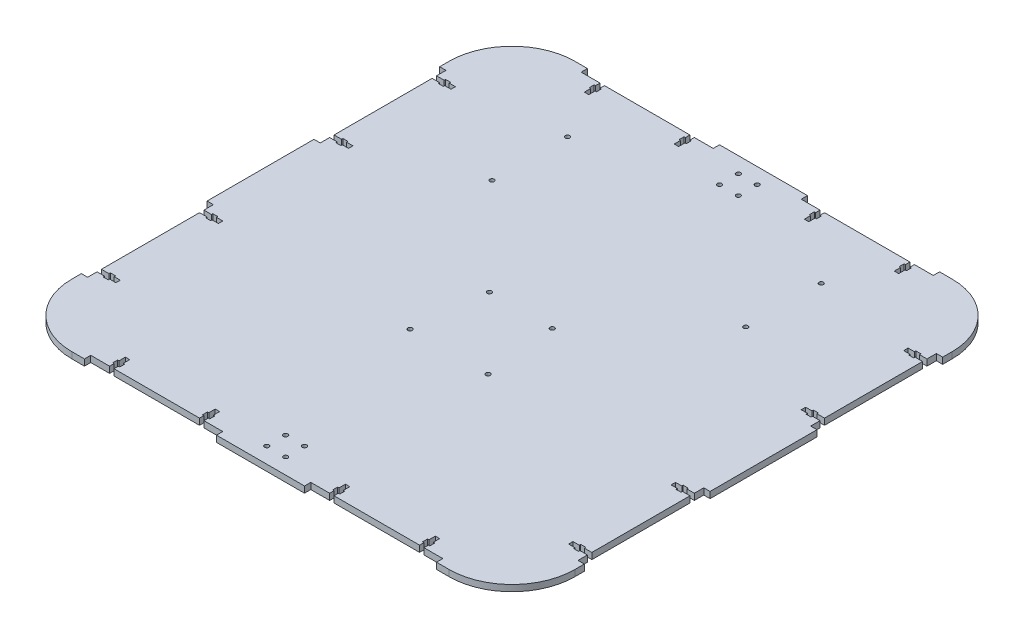
SolidWorks part; units mm, degrees
ref_plane "Front Plane" through (0, 0, 0) normal (0, 0, 1) x (1, 0, 0)
ref_plane "Top Plane" through (0, 0, 0) normal (0, 1, 0) x (1, 0, 0)
ref_plane "Right Plane" through (0, 0, 0) normal (1, 0, 0) x (0, 0, -1)
sketch "Sketch1" plane through (0, 0, 0) normal (0, 1, 0) x (1, 0, 0)
  line L0 (0, -1000) -> (0, 49000) construction
  line L9 (-1000, 0) -> (49000, 0) construction
  line L10 (-10, 190) -> (10, 190)
  line L11 (-10, 190) -> (-10, 170)
  line L12 (-10, 170) -> (10, 170)
  line L13 (10, 190) -> (10, 170)
  line L14 (-1010, 180) -> (48990, 180) construction
  line L15 (-1010, -180) -> (48990, -180) construction
  line L16 (0, 1000) -> (0, -49000) construction
  line L17 (-10, -170) -> (10, -170)
  line L18 (10, -190) -> (10, -170)
  line L19 (-10, -190) -> (10, -190)
  line L20 (-10, -190) -> (-10, -170)
  line L22 (-200, 200) -> (200, 200)
  line L23 (-200, 200) -> (-200, -200)
  line L24 (-200, -200) -> (200, -200)
  line L25 (200, 200) -> (200, -200)
  circle A0 centre (0, 0) radius 200 construction
  circle A1 centre (-7.5, 187.5) radius 1.75
  circle A2 centre (7.5, 187.5) radius 1.75
  circle A3 centre (7.5, 172.5) radius 1.75
  circle A4 centre (-7.5, 172.5) radius 1.75
  circle A5 centre (7.5, -187.5) radius 1.75
  circle A6 centre (-7.5, -187.5) radius 1.75
  circle A7 centre (-7.5, -172.5) radius 1.75
  circle A8 centre (7.5, -172.5) radius 1.75
  point P19 (0, 190)
  point P22 (-10, 180)
  dimension "D1" = 400
  dimension "D7" = 3.5
  dimension "D5" = 20
  dimension "D6" = 180
  dimension "D8" = 2.5
  dimension "D9" = 2.5
extrude "Boss-Extrude2" add sketch "Sketch1" along normal blind 5 contours L25 L22 L23 L24 L10 L13 L12 L11 L19 L20 L17 L18 | L20 L19 L18 L17 A6 A5 A7 A8 | L13 L10 L11 L12 A2 A1 A3 A4 region at (0, 0, -180) region at (0, 0, 180) region at (0, 0, 0)
fillet "Fillet1" radius 50 4 edges at (200, 2.5, -200) (200, 2.5, 200) (-200, 2.5, 200) (-200, 2.5, -200)
sketch "Sketch10" plane through (0, 5, 0) normal (0, 1, 0) x (1, 0, 0)
  line L0 (-150, -200) -> (150, -200) construction
  line L1 (-125, -200) -> (-121.5, -200)
  line L2 (-125, -200) -> (-125, -191.5)
  line L3 (-125, -182.5) -> (-121.5, -182.5)
  line L4 (-121.5, -200) -> (-121.5, -191.5)
  line L6 (-121.5, -187.5) -> (-120.4, -187.5)
  line L7 (-126.1, -187.5) -> (-125, -187.5)
  line L8 (-126.1, -187.5) -> (-126.1, -191.5)
  line L9 (-126.1, -191.5) -> (-125, -191.5)
  line L10 (-120.4, -187.5) -> (-120.4, -191.5)
  line L11 (-121.5, -191.5) -> (-120.4, -191.5)
  line L12 (-125, -187.5) -> (-125, -182.5)
  line L13 (-121.5, -187.5) -> (-121.5, -182.5)
  line L14 (-125, -187.5) -> (-121.5, -187.5) construction
  line L15 (-121.5, -191.5) -> (-125, -191.5) construction
  line L16 (-53.5, -200) -> (-50, -200)
  line L17 (-50, -200) -> (-50, -191.5)
  line L18 (-50, -191.5) -> (-48.9, -191.5)
  line L19 (-48.9, -187.5) -> (-48.9, -191.5)
  line L20 (-50, -187.5) -> (-48.9, -187.5)
  line L21 (-50, -187.5) -> (-50, -182.5)
  line L22 (-53.5, -182.5) -> (-50, -182.5)
  line L23 (-53.5, -187.5) -> (-53.5, -182.5)
  line L24 (-54.6, -187.5) -> (-53.5, -187.5)
  line L25 (-54.6, -187.5) -> (-54.6, -191.5)
  line L26 (-54.6, -191.5) -> (-53.5, -191.5)
  line L27 (-53.5, -200) -> (-53.5, -191.5)
  line L28 (-50, -191.5) -> (-53.5, -191.5) construction
  line L29 (-53.5, -187.5) -> (-50, -187.5) construction
  line L30 (0, -1200) -> (0, 48800) construction
  line L31 (-200, 150) -> (-200, -150) construction
  line L32 (121.5, -191.5) -> (125, -191.5) construction
  line L33 (125, -187.5) -> (121.5, -187.5) construction
  line L34 (125, -200) -> (125, -191.5)
  line L35 (126.1, -191.5) -> (125, -191.5)
  line L36 (126.1, -187.5) -> (126.1, -191.5)
  line L37 (126.1, -187.5) -> (125, -187.5)
  line L38 (125, -187.5) -> (125, -182.5)
  line L39 (125, -182.5) -> (121.5, -182.5)
  line L40 (121.5, -187.5) -> (121.5, -182.5)
  line L41 (121.5, -187.5) -> (120.4, -187.5)
  line L42 (120.4, -187.5) -> (120.4, -191.5)
  line L43 (121.5, -191.5) -> (120.4, -191.5)
  line L44 (121.5, -200) -> (121.5, -191.5)
  line L45 (125, -200) -> (121.5, -200)
  line L46 (53.5, -187.5) -> (50, -187.5) construction
  line L47 (50, -191.5) -> (53.5, -191.5) construction
  line L48 (53.5, -200) -> (53.5, -191.5)
  line L49 (54.6, -191.5) -> (53.5, -191.5)
  line L50 (54.6, -187.5) -> (54.6, -191.5)
  line L51 (54.6, -187.5) -> (53.5, -187.5)
  line L52 (53.5, -187.5) -> (53.5, -182.5)
  line L53 (53.5, -182.5) -> (50, -182.5)
  line L54 (50, -187.5) -> (50, -182.5)
  line L55 (50, -187.5) -> (48.9, -187.5)
  line L56 (48.9, -187.5) -> (48.9, -191.5)
  line L57 (50, -191.5) -> (48.9, -191.5)
  line L58 (50, -200) -> (50, -191.5)
  line L59 (53.5, -200) -> (50, -200)
  line L60 (-1000, 0) -> (49000, 0) construction
  line L61 (125, 200) -> (121.5, 200)
  line L62 (121.5, 200) -> (121.5, 191.5)
  line L63 (121.5, 191.5) -> (120.4, 191.5)
  line L64 (120.4, 187.5) -> (120.4, 191.5)
  line L65 (121.5, 187.5) -> (120.4, 187.5)
  line L66 (121.5, 187.5) -> (121.5, 182.5)
  line L67 (125, 182.5) -> (121.5, 182.5)
  line L68 (125, 187.5) -> (125, 182.5)
  line L69 (126.1, 187.5) -> (125, 187.5)
  line L70 (126.1, 187.5) -> (126.1, 191.5)
  line L71 (126.1, 191.5) -> (125, 191.5)
  line L72 (125, 200) -> (125, 191.5)
  line L73 (53.5, 200) -> (50, 200)
  line L74 (50, 200) -> (50, 191.5)
  line L75 (50, 191.5) -> (48.9, 191.5)
  line L76 (48.9, 187.5) -> (48.9, 191.5)
  line L77 (50, 187.5) -> (48.9, 187.5)
  line L78 (50, 187.5) -> (50, 182.5)
  line L79 (53.5, 182.5) -> (50, 182.5)
  line L80 (53.5, 187.5) -> (53.5, 182.5)
  line L81 (54.6, 187.5) -> (53.5, 187.5)
  line L82 (54.6, 187.5) -> (54.6, 191.5)
  line L83 (54.6, 191.5) -> (53.5, 191.5)
  line L84 (53.5, 200) -> (53.5, 191.5)
  line L85 (-53.5, 200) -> (-53.5, 191.5)
  line L86 (-54.6, 191.5) -> (-53.5, 191.5)
  line L87 (-54.6, 187.5) -> (-54.6, 191.5)
  line L88 (-54.6, 187.5) -> (-53.5, 187.5)
  line L89 (-53.5, 187.5) -> (-53.5, 182.5)
  line L90 (-53.5, 182.5) -> (-50, 182.5)
  line L91 (-50, 187.5) -> (-50, 182.5)
  line L92 (-50, 187.5) -> (-48.9, 187.5)
  line L93 (-48.9, 187.5) -> (-48.9, 191.5)
  line L94 (-50, 191.5) -> (-48.9, 191.5)
  line L95 (-50, 200) -> (-50, 191.5)
  line L96 (-53.5, 200) -> (-50, 200)
  line L97 (-125, 200) -> (-125, 191.5)
  line L98 (-126.1, 191.5) -> (-125, 191.5)
  line L99 (-126.1, 187.5) -> (-126.1, 191.5)
  line L100 (-126.1, 187.5) -> (-125, 187.5)
  line L101 (-125, 187.5) -> (-125, 182.5)
  line L102 (-125, 182.5) -> (-121.5, 182.5)
  line L103 (-121.5, 187.5) -> (-121.5, 182.5)
  line L104 (-121.5, 187.5) -> (-120.4, 187.5)
  line L105 (-120.4, 187.5) -> (-120.4, 191.5)
  line L106 (-121.5, 191.5) -> (-120.4, 191.5)
  line L107 (-121.5, 200) -> (-121.5, 191.5)
  line L108 (-125, 200) -> (-121.5, 200)
  point P11 (-123.25, -200)
  point P15 (-123.25, -191.5)
  point P16 (-123.25, -187.5)
  point P17 (-123.25, -182.5)
  point P33 (0, -200)
  dimension "D1" = 3.5
  dimension "D2" = 5.7
  dimension "D3" = 5
  dimension "D4" = 4
  dimension "D5" = 1.1
  dimension "D7" = 75
  dimension "D8" = 50
  dimension "D9" = 17.5
  dimension "D6" = 2
extrude "Cut-Extrude8" cut sketch "Sketch10" against normal blind 10
sketch "Sketch11" plane through (0, 5, 0) normal (0, 1, 0) x (1, 0, 0)
  line L0 (-150, -200) -> (-125, -200) construction
  line L1 (-140, -200) -> (-35, -200)
  line L2 (-140, -200) -> (-140, -195)
  line L3 (-140, -195) -> (-35, -195)
  line L4 (-35, -200) -> (-35, -195)
  line L5 (-50, -200) -> (-50, -191.5) construction
  line L6 (-125, -191.5) -> (-125, -200) construction
  line L7 (0, -1200) -> (0, 48800) construction
  line L8 (-50, -200) -> (50, -200) construction
  line L9 (-1200, 0) -> (48800, 0) construction
  line L10 (-200, 150) -> (-200, -150) construction
  line L11 (140, -195) -> (35, -195)
  line L12 (35, -200) -> (35, -195)
  line L13 (140, -200) -> (35, -200)
  line L14 (140, -200) -> (140, -195)
  line L15 (140, 200) -> (140, 195)
  line L16 (140, 200) -> (35, 200)
  line L17 (35, 200) -> (35, 195)
  line L18 (140, 195) -> (35, 195)
  line L19 (-140, 195) -> (-35, 195)
  line L20 (-35, 200) -> (-35, 195)
  line L21 (-140, 200) -> (-35, 200)
  line L22 (-140, 200) -> (-140, 195)
  point P15 (0, -200)
  point P20 (-200, 0)
  dimension "D1" = 5
  dimension "D2" = 15
  dimension "D3" = 15
extrude "Cut-Extrude9" cut sketch "Sketch11" against normal blind 10
sketch "Sketch12" plane through (0, 5, 0) normal (0, 1, 0) x (1, 0, 0)
  line L0 (-200, 150) -> (-200, -150) construction
  line L1 (-200, 135) -> (-189, 135)
  line L2 (-200, 135) -> (-200, 131.5)
  line L3 (-200, 131.5) -> (-189, 131.5)
  line L4 (-180, 135) -> (-180, 131.5)
  line L5 (-200, 53.5) -> (-189, 53.5)
  line L6 (-189, 131.5) -> (-189, 130.4)
  line L7 (-189, 136.1) -> (-185, 136.1)
  line L8 (-189, 136.1) -> (-189, 135)
  line L9 (-189, 130.4) -> (-185, 130.4)
  line L10 (-185, 136.1) -> (-185, 135)
  line L11 (-185, 131.5) -> (-185, 130.4)
  line L12 (-185, 135) -> (-180, 135)
  line L13 (-185, 131.5) -> (-180, 131.5)
  line L14 (-189, 135) -> (-189, 131.5) construction
  line L15 (-185, 131.5) -> (-185, 135) construction
  line L16 (-189, 54.6) -> (-189, 53.5)
  line L17 (-189, 54.6) -> (-185, 54.6)
  line L18 (-185, 54.6) -> (-185, 53.5)
  line L19 (-185, 53.5) -> (-180, 53.5)
  line L20 (-180, 53.5) -> (-180, 50)
  line L21 (-185, 50) -> (-180, 50)
  line L22 (-185, 50) -> (-185, 48.9)
  line L23 (-189, 48.9) -> (-185, 48.9)
  line L24 (-189, 50) -> (-189, 48.9)
  line L25 (-200, 50) -> (-189, 50)
  line L26 (-200, 53.5) -> (-200, 50)
  line L27 (-1200, 0) -> (48800, 0) construction
  line L28 (-200, -53.5) -> (-200, -50)
  line L29 (-200, -50) -> (-189, -50)
  line L30 (-189, -50) -> (-189, -48.9)
  line L31 (-189, -48.9) -> (-185, -48.9)
  line L32 (-185, -50) -> (-185, -48.9)
  line L33 (-185, -50) -> (-180, -50)
  line L34 (-180, -53.5) -> (-180, -50)
  line L35 (-185, -53.5) -> (-180, -53.5)
  line L36 (-185, -54.6) -> (-185, -53.5)
  line L37 (-189, -54.6) -> (-185, -54.6)
  line L38 (-189, -54.6) -> (-189, -53.5)
  line L39 (-200, -53.5) -> (-189, -53.5)
  line L40 (-200, -135) -> (-200, -131.5)
  line L41 (-200, -131.5) -> (-189, -131.5)
  line L42 (-189, -131.5) -> (-189, -130.4)
  line L43 (-189, -130.4) -> (-185, -130.4)
  line L44 (-185, -131.5) -> (-185, -130.4)
  line L45 (-185, -131.5) -> (-180, -131.5)
  line L46 (-180, -135) -> (-180, -131.5)
  line L47 (-185, -135) -> (-180, -135)
  line L48 (-185, -136.1) -> (-185, -135)
  line L49 (-189, -136.1) -> (-185, -136.1)
  line L50 (-189, -136.1) -> (-189, -135)
  line L51 (-200, -135) -> (-189, -135)
  line L52 (0, -1200) -> (0, 48800) construction
  line L53 (-35, -200) -> (35, -200) construction
  line L54 (200, -135) -> (189, -135)
  line L55 (189, -136.1) -> (189, -135)
  line L56 (189, -136.1) -> (185, -136.1)
  line L57 (185, -136.1) -> (185, -135)
  line L58 (185, -135) -> (180, -135)
  line L59 (180, -135) -> (180, -131.5)
  line L60 (185, -131.5) -> (180, -131.5)
  line L61 (185, -131.5) -> (185, -130.4)
  line L62 (189, -130.4) -> (185, -130.4)
  line L63 (189, -131.5) -> (189, -130.4)
  line L64 (200, -131.5) -> (189, -131.5)
  line L65 (200, -135) -> (200, -131.5)
  line L66 (200, -53.5) -> (189, -53.5)
  line L67 (189, -54.6) -> (189, -53.5)
  line L68 (189, -54.6) -> (185, -54.6)
  line L69 (185, -54.6) -> (185, -53.5)
  line L70 (185, -53.5) -> (180, -53.5)
  line L71 (180, -53.5) -> (180, -50)
  line L72 (185, -50) -> (180, -50)
  line L73 (185, -50) -> (185, -48.9)
  line L74 (189, -48.9) -> (185, -48.9)
  line L75 (189, -50) -> (189, -48.9)
  line L76 (200, -50) -> (189, -50)
  line L77 (200, -53.5) -> (200, -50)
  line L78 (200, 53.5) -> (200, 50)
  line L79 (200, 50) -> (189, 50)
  line L80 (189, 50) -> (189, 48.9)
  line L81 (189, 48.9) -> (185, 48.9)
  line L82 (185, 50) -> (185, 48.9)
  line L83 (185, 50) -> (180, 50)
  line L84 (180, 53.5) -> (180, 50)
  line L85 (185, 53.5) -> (180, 53.5)
  line L86 (185, 54.6) -> (185, 53.5)
  line L87 (189, 54.6) -> (185, 54.6)
  line L88 (189, 54.6) -> (189, 53.5)
  line L89 (200, 53.5) -> (189, 53.5)
  line L90 (200, 135) -> (200, 131.5)
  line L91 (200, 131.5) -> (189, 131.5)
  line L92 (189, 131.5) -> (189, 130.4)
  line L93 (189, 130.4) -> (185, 130.4)
  line L94 (185, 131.5) -> (185, 130.4)
  line L95 (185, 131.5) -> (180, 131.5)
  line L96 (180, 135) -> (180, 131.5)
  line L97 (185, 135) -> (180, 135)
  line L98 (185, 136.1) -> (185, 135)
  line L99 (189, 136.1) -> (185, 136.1)
  line L100 (189, 136.1) -> (189, 135)
  line L101 (200, 135) -> (189, 135)
  point P31 (-200, 0)
  point P60 (0, -200)
  dimension "D1" = 20
  dimension "D2" = 3.5
  dimension "D3" = 5.7
  dimension "D4" = 5
  dimension "D5" = 4
  dimension "D6" = 15
  dimension "D7" = 1.1
  dimension "D9" = 50
  dimension "D8" = 2
extrude "Cut-Extrude10" cut sketch "Sketch12" against normal blind 5
sketch "Sketch13" plane through (0, 5, 0) normal (0, 1, 0) x (1, 0, 0)
  line L0 (-200, 150) -> (-200, 135) construction
  line L1 (-200, 142.5) -> (-195, 142.5)
  line L2 (-200, 142.5) -> (-200, 42.5)
  line L3 (-200, 42.5) -> (-195, 42.5)
  line L4 (-195, 142.5) -> (-195, 42.5)
  line L6 (-200, 50) -> (-189, 50) construction
  line L7 (-1200, 0) -> (48800, 0) construction
  line L8 (-200, 50) -> (-200, -50) construction
  line L9 (0, -800) -> (0, 49200) construction
  line L10 (-35, 200) -> (35, 200) construction
  line L11 (-200, -42.5) -> (-195, -42.5)
  line L12 (-195, -142.5) -> (-195, -42.5)
  line L13 (-200, -142.5) -> (-195, -142.5)
  line L14 (-200, -142.5) -> (-200, -42.5)
  line L15 (0, 800) -> (0, -49200) construction
  line L16 (200, -142.5) -> (200, -42.5)
  line L17 (200, -142.5) -> (195, -142.5)
  line L18 (195, -142.5) -> (195, -42.5)
  line L19 (200, -42.5) -> (195, -42.5)
  line L20 (200, 42.5) -> (195, 42.5)
  line L21 (195, 142.5) -> (195, 42.5)
  line L22 (200, 142.5) -> (195, 142.5)
  line L23 (200, 142.5) -> (200, 42.5)
  point P13 (-200, 0)
  point P18 (0, 200)
  dimension "D1" = 7.5
  dimension "D2" = 5
extrude "Cut-Extrude11" cut sketch "Sketch13" against normal blind 5
sketch "Sketch14" plane through (0, 5, 0) normal (0, 1, 0) x (1, 0, 0)
  line L0 (-31, -50) -> (31, -50) construction
  line L1 (-25, 7) -> (25, 7) construction
  circle A0 centre (-31, -50) radius 1.75
  circle A1 centre (31, -50) radius 1.75
  circle A2 centre (-25, 7) radius 1.75
  circle A3 centre (25, 7) radius 1.75
  point P4 (0, -50)
  point P7 (0, 7)
  dimension "D1" = 3.5
  dimension "D2" = 62
  dimension "D3" = 50
  dimension "D4" = 50
  dimension "D5" = 57
extrude "Cut-Extrude12" cut sketch "Sketch14" against normal blind 10
sketch "Sketch15" plane through (0, 5, 0) normal (0, 1, 0) x (1, 0, 0)
  line L0 (-140, 195) -> (-125, 195) construction
  line L2 (0, -800) -> (0, 49200) construction
  line L3 (-35, 200) -> (35, 200) construction
  circle A0 centre (-100.9, 145) radius 1.75
  circle A2 centre (-100.9, 85) radius 1.75
  circle A4 centre (100.9, 85) radius 1.75
  circle A5 centre (100.9, 145) radius 1.75
  point P10 (0, 200)
  dimension "D1" = 3.5
  dimension "D2" = 60
  dimension "D3" = 201.8
  dimension "D4" = 50
extrude "Cut-Extrude13" cut sketch "Sketch15" against normal blind 10
